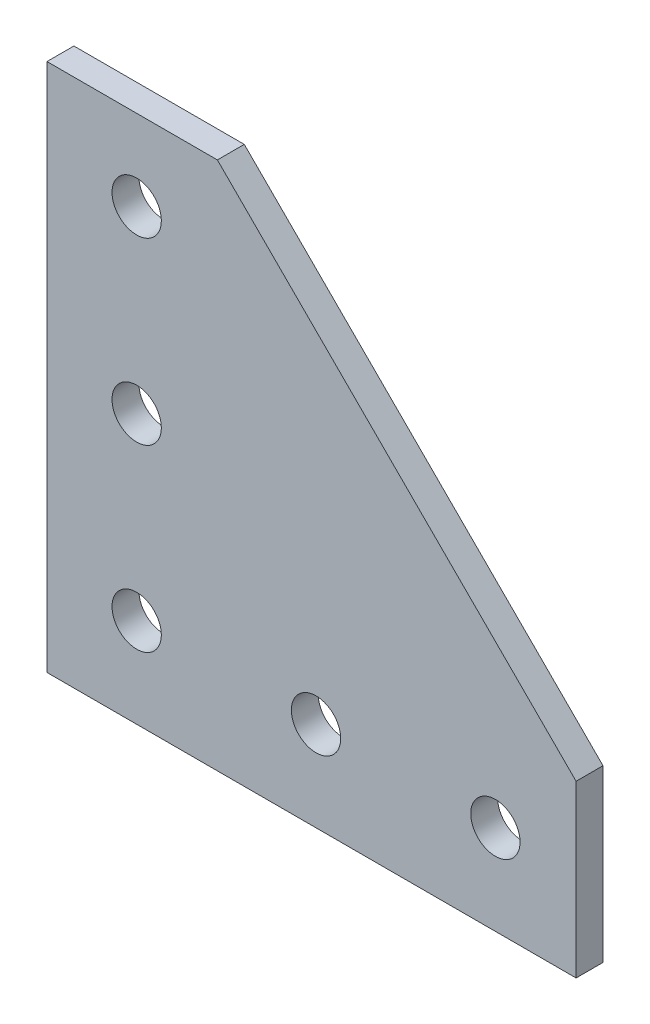
SolidWorks part; units mm, degrees
ref_plane "Piano frontale" through (0, 0, 0) normal (0, 0, 1) x (1, 0, 0)
ref_plane "Piano superiore" through (0, 0, 0) normal (0, 1, 0) x (1, 0, 0)
ref_plane "Piano destro" through (0, 0, 0) normal (1, 0, 0) x (0, 0, -1)
sketch "Schizzo1" plane through (0, 0, 0) normal (0, 0, 1) x (1, 0, 0)
  line L1 (0, 0) -> (59, 0)
  line L2 (0, 0) -> (0, 59)
  line L3 (0, 59) -> (59, 59)
  line L4 (59, 0) -> (59, 59)
  dimension "D1" = 59
  dimension "D2" = 59
extrude "Estrusione-Estrusione1" add sketch "Schizzo1" along normal blind 3
hole_wizard "Foro per Vite M5-1" positions "Schizzo4" profile "Schizzo3" hole size "M5" standard "DIN" end condition through all
sketch "Schizzo4" plane through (0, 0, 3) normal (0, 0, 1) x (1, 0, 0)
  line L0 (10, 50) -> (10, 10) construction
  line L1 (10, 10) -> (50, 10) construction
  line L3 (0, 59) -> (0, 0) construction
  line L4 (0, 0) -> (59, 0) construction
  point P0 (10, 10)
  point P2 (10, 30)
  point P4 (30, 10)
  point P6 (50, 10)
  point P8 (10, 50)
  dimension "D1" = 10
  dimension "D2" = 10
  dimension "D3" = 20
  dimension "D4" = 20
  dimension "D5" = 20
  dimension "D6" = 20
sketch "Schizzo3" plane through (10, 10, 3) normal (1, 0, 0) x (0, -1, 0)
  line L0 (0, 0) -> (0, 3)
  line L1 (0, 3) -> (2.75, 3)
  line L2 (2.75, 3) -> (2.75, 0)
  line L5 (2.75, 0) -> (0, 0)
  line L11 (0, -6.35) -> (0, 107.95) construction
  dimension "Thru Hole Dia." = 5.5
  dimension "Thru Hole Depth" = 3
chamfer "Smusso1" distance 40 angle 45 1 edges at (59, 59, 1.5)
ref_axis "Assi1" through (10, 10, 0) along (0, 0, 1)
ref_plane "Piano1" through (0, 10, 0) normal (0, -1, 0) x (-1, 0, 0)
ref_plane "Piano2" through (10, 0, 0) normal (-1, 0, 0) x (0, 0, 1)
